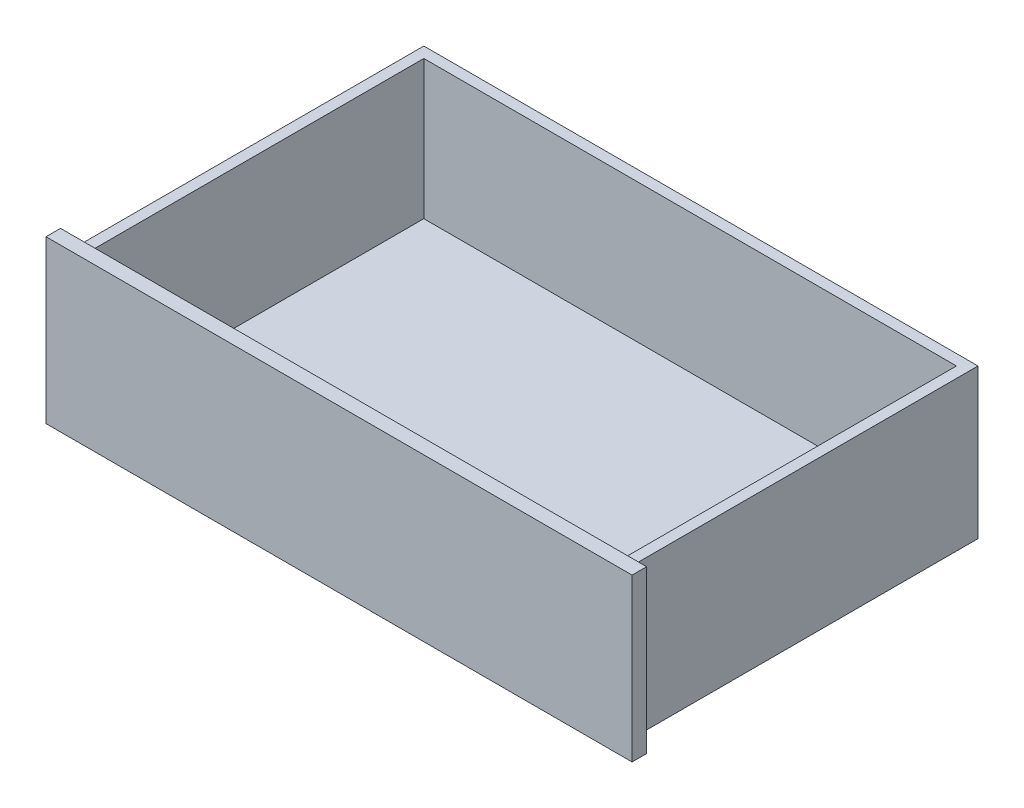
SolidWorks part; units mm, degrees
material "Maple"
ref_plane "Front Plane" through (0, 0, 0) normal (0, 0, 1) x (1, 0, 0)
ref_plane "Top Plane" through (0, 0, 0) normal (0, 1, 0) x (1, 0, 0)
ref_plane "Right Plane" through (0, 0, 0) normal (1, 0, 0) x (0, 0, -1)
sketch "Sketch1" plane through (0, 0, 0) normal (0, 1, 0) x (1, 0, 0)
  line L1 (-315, -200) -> (315, -200)
  line L2 (-315, -200) -> (-315, 200)
  line L3 (-315, 200) -> (315, 200)
  line L4 (315, -200) -> (315, 200)
  line L5 (-315, -200) -> (315, 200) construction
  line L6 (-315, 200) -> (315, -200) construction
  point P0 (0, 0)
  dimension "D1" = 630
  dimension "D2" = 400
extrude "Extrusion" add sketch "Sketch1" along normal blind 170
shell "Drawer's interior" thickness 12.2428 removed face at (0, 170, 0)
sketch "Sketch2" plane through (0, 0, 200) normal (0, 0, 1) x (1, 0, 0)
  line L0 (-315, 0) -> (315, 0) construction
  line L1 (-351.5, -5) -> (351.5, -5)
  line L2 (-351.5, -5) -> (-351.5, 175)
  line L3 (-351.5, 175) -> (351.5, 175)
  line L4 (351.5, -5) -> (351.5, 175)
  line L5 (-351.5, -5) -> (351.5, 175) construction
  line L6 (-351.5, 175) -> (351.5, -5) construction
  line L7 (315, 170) -> (315, 0) construction
  point P0 (0, 85)
  point P8 (0, 0)
  point P14 (315, 85)
  dimension "D1" = 703
  dimension "D2" = 180
extrude "Boss-Extrude2" [suppressed] add sketch "Sketch2" along normal blind 17 contours L4 L3 L2 L1
sketch "Sketch3" plane through (0, 0, 200) normal (0, 0, 1) x (1, 0, 0)
  line L0 (315, 170) -> (315, 0) construction
  line L1 (-328, 184) -> (338.2428, 184)
  line L2 (-328, 184) -> (-328, 0)
  line L4 (338.2428, 184) -> (338.2428, 0)
  line L5 (-315, 170) -> (-315, 0) construction
  line L6 (-315, 170) -> (315, 170) construction
  line L8 (-328, 0) -> (338.2428, 0)
  line L9 (-315, 0) -> (315, 0) construction
  dimension "D1" = 23.2428
  dimension "D2" = 13
  dimension "D3" = 14
  dimension "D4" = 0
extrude "Boss-Extrude3" add sketch "Sketch3" along normal blind 16.5
equation "\"D1@Drawer's interior\"=\"Drawer_side_tickness@Drawer Assembly Narrow.Assembly\""
equation "\"D2@Sketch1\"=\"Drawer_length@Drawer Assembly Narrow.Assembly\""
equation "\"D3@Sketch3\"=\"Drawer_top_clearance@Drawer Assembly Narrow.Assembly\""
equation "\"D1@Sketch3\"=\"Drawer­_to_sidewall@Drawer Assembly Narrow.Assembly\"+\"Drawer_side_tickness@Drawer Assembly Narrow.Assembly\""
